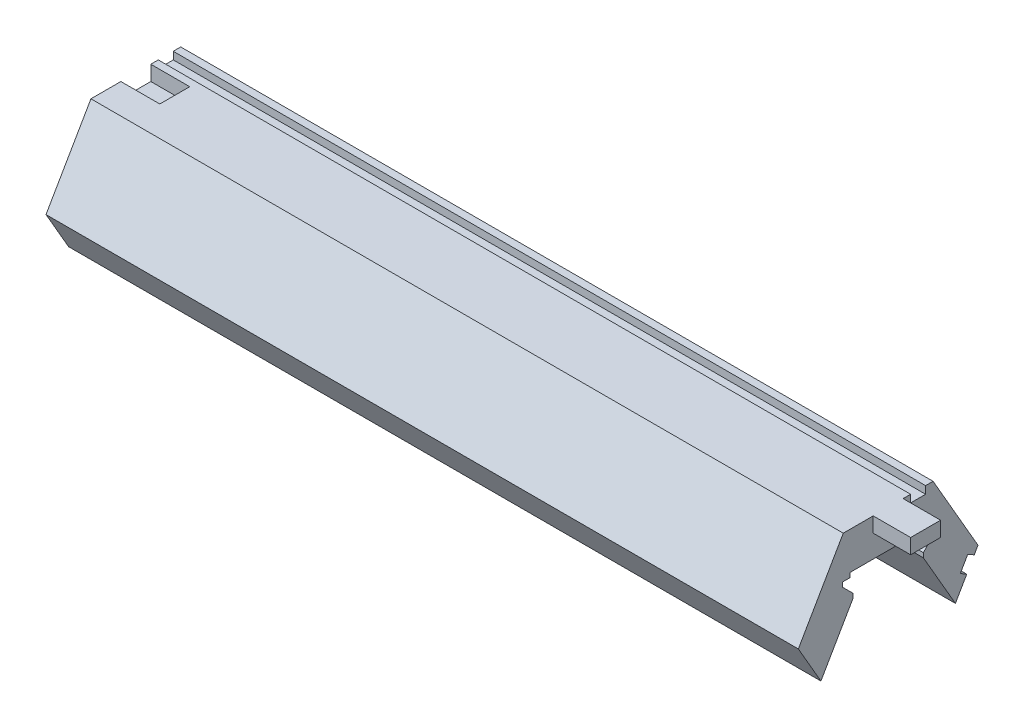
SolidWorks part; units mm, degrees
ref_plane "Front Plane" through (0, 0, 0) normal (0, 0, 1) x (1, 0, 0)
ref_plane "Top Plane" through (0, 0, 0) normal (0, 1, 0) x (1, 0, 0)
ref_plane "Right Plane" through (0, 0, 0) normal (1, 0, 0) x (0, 0, -1)
sketch "Master Design Profile" plane through (0, 0, 0) normal (1, 0, 0) x (0, 0, -1)
  line L0 (-5.1, 5.3923) -> (5.1, 5.3923)
  line L1 (12, 0) -> (6, 10.3923)
  line L2 (6, 10.3923) -> (-6, 10.3923)
  line L3 (-6, 10.3923) -> (-12, 0)
  line L4 (-12, 0) -> (-8.9829, -5.2258)
  line L5 (0, -10.3923) -> (6, -10.3923) construction
  line L6 (8.9829, -5.2258) -> (12, 0)
  line L7 (-5.1, 5.3923) -> (-5.1, 4.7923)
  line L8 (-5.1, 4.7923) -> (-6.1, 4.7923)
  line L9 (0, -28.6883) -> (0, 28.6883) construction
  line L10 (-6.1, 4.7923) -> (-6.1, 4.1923)
  line L11 (-6.1, 4.1923) -> (-4.7, 2.7923)
  line L13 (-4.7, 2.7923) -> (-4.7, 2.1923)
  line L14 (-4.7, 2.1923) -> (-8.9829, -5.2258)
  line L15 (4.7, 2.1923) -> (8.9829, -5.2258)
  line L16 (4.7, 2.7923) -> (4.7, 2.1923)
  line L17 (6.1, 4.1923) -> (4.7, 2.7923)
  line L18 (6.1, 4.7923) -> (6.1, 4.1923)
  line L19 (5.1, 4.7923) -> (6.1, 4.7923)
  line L20 (5.1, 5.3923) -> (5.1, 4.7923)
  line L21 (-9, -5.1962) -> (-6, -10.3923) construction
  line L22 (-8.9829, -5.2258) -> (-9, -5.1962) construction
  line L23 (-6, -10.3923) -> (0, -10.3923) construction
  line L24 (6, -10.3923) -> (9, -5.1962) construction
  line L25 (9, -5.1962) -> (8.9829, -5.2258) construction
  circle A0 centre (0, 0) radius 10.3923 construction
  point P15 (0, 0)
  point P16 (0, 5.3923)
  dimension "D1" = 10.2
  dimension "D2" = 0.6
  dimension "D3" = 0.6
  dimension "D4" = 1
  dimension "D5" = 135
  dimension "D6" = 2
  dimension "D7" = 5
  dimension "D8" = 210
  dimension "D9" = 0.6
  dimension "D10" = 12
sketch "LED Groove Profile Test" plane through (0, 0, 0) normal (1, 0, 0) x (0, 0, -1)
  line L0 (4.7, 2.7923) -> (4.7, 2.1923) construction
  line L1 (6.1, 4.1923) -> (4.7, 2.7923) construction
  line L2 (6.1, 4.7923) -> (6.1, 4.1923) construction
  line L3 (5.1, 4.7923) -> (6.1, 4.7923) construction
  line L4 (5.1, 5.3923) -> (5.1, 4.7923) construction
  line L5 (-5.1, 5.3923) -> (5.1, 5.3923) construction
  line L6 (-5.1, 5.3923) -> (-5.1, 4.7923) construction
  line L7 (-5.1, 4.7923) -> (-6.1, 4.7923) construction
  line L8 (-6.1, 4.7923) -> (-6.1, 4.1923) construction
  line L9 (-6.1, 4.1923) -> (-4.7, 2.7923) construction
  line L10 (-4.7, 2.7923) -> (-4.7, 2.1923) construction
  line L11 (-4.7, 2.7923) -> (-4.7, 2.1923)
  line L12 (-6.1, 4.1923) -> (-4.7, 2.7923)
  line L13 (-6.1, 4.7923) -> (-6.1, 4.1923)
  line L14 (-5.1, 4.7923) -> (-6.1, 4.7923)
  line L15 (-5.1, 5.3923) -> (-5.1, 4.7923)
  line L16 (-5.1, 5.3923) -> (5.1, 5.3923)
  line L17 (5.1, 5.3923) -> (5.1, 4.7923)
  line L18 (5.1, 4.7923) -> (6.1, 4.7923)
  line L19 (6.1, 4.7923) -> (6.1, 4.1923)
  line L20 (6.1, 4.1923) -> (4.7, 2.7923)
  line L21 (4.7, 2.7923) -> (4.7, 2.1923)
  line L22 (-4.7, 2.1923) -> (-7.5, 2.1923)
  line L23 (-7.5, 2.1923) -> (-7.5, 7.1923)
  line L24 (-7.5, 7.1923) -> (7.5, 7.1923)
  line L25 (7.5, 7.1923) -> (7.5, 2.1923)
  line L26 (7.5, 2.1923) -> (4.7, 2.1923)
  line L27 (0, -28.6883) -> (0, 28.6883) construction
  point P0 (0, 7.1923)
  dimension "D1" = 5
  dimension "D2" = 15
extrude "Boss-Extrude1" [suppressed] add sketch "LED Groove Profile Test" along normal mid plane 15
sketch "LED Segment" plane through (0, 0, 0) normal (1, 0, 0) x (0, 0, -1)
  line L0 (8.9829, -5.2258) -> (12, 0) construction
  line L1 (12, 0) -> (6, 10.3923) construction
  line L2 (6, 10.3923) -> (-6, 10.3923) construction
  line L3 (-6, 10.3923) -> (-12, 0) construction
  line L4 (-12, 0) -> (-8.9829, -5.2258) construction
  line L5 (-4.7, 2.1923) -> (-8.9829, -5.2258) construction
  line L6 (4.7, 2.1923) -> (8.9829, -5.2258) construction
  line L7 (4.7, 2.7923) -> (4.7, 2.1923) construction
  line L8 (6.1, 4.1923) -> (4.7, 2.7923) construction
  line L9 (6.1, 4.7923) -> (6.1, 4.1923) construction
  line L10 (5.1, 4.7923) -> (6.1, 4.7923) construction
  line L11 (5.1, 5.3923) -> (5.1, 4.7923) construction
  line L12 (-5.1, 5.3923) -> (5.1, 5.3923) construction
  line L13 (-5.1, 5.3923) -> (-5.1, 4.7923) construction
  line L14 (-5.1, 4.7923) -> (-6.1, 4.7923) construction
  line L15 (-6.1, 4.7923) -> (-6.1, 4.1923) construction
  line L16 (-4.7, 2.7923) -> (-4.7, 2.1923) construction
  line L17 (-6.1, 4.1923) -> (-4.7, 2.7923) construction
  line L18 (8.9829, -5.2258) -> (12, 0)
  line L19 (12, 0) -> (6, 10.3923)
  line L20 (6, 10.3923) -> (-6, 10.3923)
  line L21 (-6, 10.3923) -> (-12, 0)
  line L22 (-12, 0) -> (-8.9829, -5.2258)
  line L23 (-4.7, 2.1923) -> (-8.9829, -5.2258)
  line L24 (4.7, 2.1923) -> (8.9829, -5.2258)
  line L25 (4.7, 2.7923) -> (4.7, 2.1923)
  line L26 (6.1, 4.1923) -> (4.7, 2.7923)
  line L27 (6.1, 4.7923) -> (6.1, 4.1923)
  line L28 (5.1, 4.7923) -> (6.1, 4.7923)
  line L29 (5.1, 5.3923) -> (5.1, 4.7923)
  line L30 (-5.1, 5.3923) -> (5.1, 5.3923)
  line L31 (-5.1, 5.3923) -> (-5.1, 4.7923)
  line L32 (-5.1, 4.7923) -> (-6.1, 4.7923)
  line L33 (-6.1, 4.7923) -> (-6.1, 4.1923)
  line L34 (-4.7, 2.7923) -> (-4.7, 2.1923)
  line L35 (-6.1, 4.1923) -> (-4.7, 2.7923)
extrude "Boss-Extrude2" add sketch "LED Segment" along normal mid plane 100.5
sketch "Sketch3" plane through (50.25, 0, 0) normal (1, 0, 0) x (0, 0, -1)
  line L5 (5, 10.3923) -> (5, 9.3923)
  line L11 (6, 10.3923) -> (-6, 10.3923) construction
  line L12 (5, 9.3923) -> (3, 9.3923)
  line L13 (3, 9.3923) -> (3, 10.3923)
  line L14 (3, 10.3923) -> (5, 10.3923)
  line L15 (12, 0) -> (6, 10.3923) construction
  line L16 (12, 0) -> (6, 10.3923) construction
  line L17 (11.6944, 6.7518) -> (6.3056, 3.6405) construction
  line L18 (10.5, -2.5981) -> (11.5, -0.866)
  line L19 (9.634, -2.0981) -> (10.5, -2.5981)
  line L20 (10.634, -0.366) -> (9.634, -2.0981)
  line L21 (11.5, -0.866) -> (10.634, -0.366)
  point P12 (9, 5.1962)
  dimension "D1" = 1
  dimension "D2" = 1
  dimension "D3" = 2
extrude "Cut-Extrude2" cut sketch "Sketch3" against normal through all
sketch "Sketch4" plane through (50.25, 0, 0) normal (1, 0, 0) x (0, 0, -1)
  line L0 (3, 10.3923) -> (-6, 10.3923) construction
  line L1 (2, 10.3923) -> (-2, 10.3923)
  line L2 (2, 10.3923) -> (2, 8.3923)
  line L3 (2, 8.3923) -> (-2, 8.3923)
  line L4 (-2, 10.3923) -> (-2, 8.3923)
  line L5 (0, 10.3923) -> (0, 5.3923) construction
  line L6 (-5.1, 5.3923) -> (5.1, 5.3923) construction
  point P10 (0, 0)
  point P11 (0, 0)
  dimension "D1" = 4
  dimension "D2" = 2
extrude "Boss-Extrude3" add sketch "Sketch4" along normal blind 5
sketch "Sketch5" plane through (-50.25, 0, 0) normal (-1, 0, 0) x (0, 0, 1)
  line L1 (-2, 10.3923) -> (-2, 8.3923)
  line L2 (2, 8.3923) -> (2, 10.3923)
  line L4 (2, 10.3923) -> (-2, 10.3923)
  line L5 (2, 8.3923) -> (2, 10.3923)
  line L6 (-2, 8.3923) -> (2, 8.3923)
  line L7 (-2, 10.3923) -> (-2, 8.3923)
  line L8 (2, 10.3923) -> (-2, 10.3923)
  line L10 (-2, 8.3923) -> (2, 8.3923)
  dimension "D1" = 0
extrude "Cut-Extrude3" cut sketch "Sketch5" against normal blind 5.2
